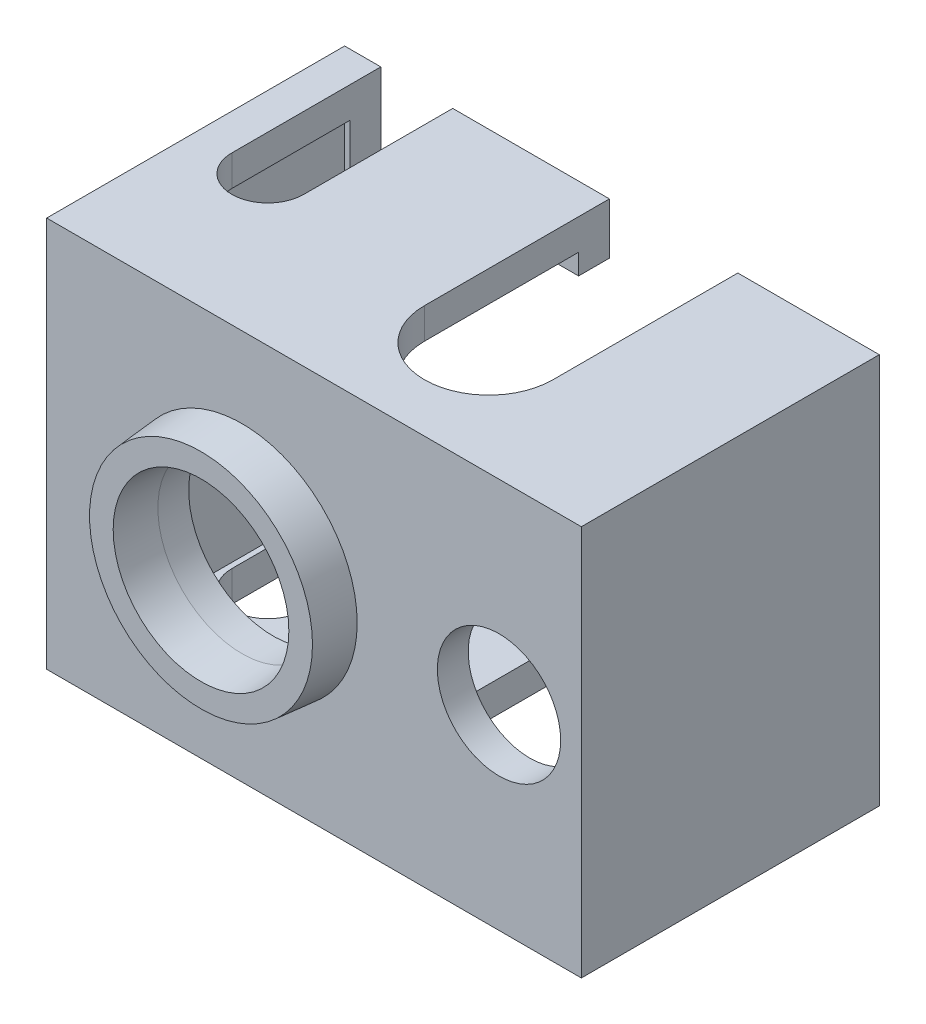
SolidWorks part; units mm, degrees
material "Silicon"
ref_plane "Front Plane" through (0, 0, 0) normal (0, 0, 1) x (1, 0, 0)
ref_plane "Top Plane" through (0, 0, 0) normal (0, 1, 0) x (1, 0, 0)
ref_plane "Right Plane" through (0, 0, 0) normal (1, 0, 0) x (0, 0, -1)
sketch "Sketch1" plane through (0, 0, 0) normal (0, 0, 1) x (1, 0, 0)
  line L0 (0, 0) -> (15.01, 0) construction
  line L1 (0, 0) -> (0, -8.01) construction
  line L2 (15, -7.5) -> (15, 7.5) construction
  line L3 (15.01, 8.01) -> (-8.01, 8.01)
  line L4 (15.01, 8.01) -> (15.01, -8.01)
  line L5 (15.01, -8.01) -> (-8.01, -8.01)
  line L6 (-8.01, 8.01) -> (-8.01, -8.01)
  line L7 (-8, -7.5) -> (-8, 7.5) construction
  line L8 (14.5, -8) -> (-7.5, -8) construction
  line L9 (-9.51, 9.51) -> (-9.51, -9.51)
  line L10 (16.51, -9.51) -> (-9.51, -9.51)
  line L11 (16.51, 9.51) -> (16.51, -9.51)
  line L12 (16.51, 9.51) -> (-9.51, 9.51)
  point P8 (15.01, 0)
  point P9 (0, -9.3747)
  point P20 (-11.0812, -11.0812)
  dimension "D1" = 0.01
  dimension "D2" = 0.01
  dimension "D3" = 0.01
  dimension "D4" = 1.5
extrude "Boss-Extrude1" add sketch "Sketch1" against normal blind 11.5
sketch "Sketch2" plane through (0, 0, -11.5) normal (0, 0, -1) x (-1, 0, 0)
  line L4 (9.51, 9.51) -> (-16.51, 9.51)
  line L5 (-16.51, 9.51) -> (-16.51, -9.51)
  line L6 (-16.51, -9.51) -> (9.51, -9.51)
  line L7 (9.51, -9.51) -> (9.51, 9.51)
  line L8 (9.51, 9.51) -> (-16.51, 9.51)
  line L9 (-16.51, 9.51) -> (-16.51, -9.51)
  line L10 (-16.51, -9.51) -> (9.51, -9.51)
  line L11 (9.51, -9.51) -> (9.51, 9.51)
  line L22 (7.01, -7.01) -> (7.01, 7.01)
  line L23 (-14.01, -7.01) -> (7.01, -7.01)
  line L24 (-14.01, 7.01) -> (-14.01, -7.01)
  line L25 (7.01, 7.01) -> (-14.01, 7.01)
  line L26 (7.01, -7.01) -> (7.01, 7.01)
  line L27 (-14.01, -7.01) -> (7.01, -7.01)
  line L28 (-14.01, 7.01) -> (-14.01, -7.01)
  line L29 (7.01, 7.01) -> (-14.01, 7.01)
  dimension "D1" = 0
  dimension "D2" = 1
extrude "Boss-Extrude2" add sketch "Sketch2" along normal blind 1.5
sketch "Sketch3" plane through (0, 0, 0) normal (0, 0, 1) x (1, 0, 0)
  line L4 (16.51, 9.51) -> (-9.51, 9.51)
  line L5 (-9.51, 9.51) -> (-9.51, -9.51)
  line L6 (-9.51, -9.51) -> (16.51, -9.51)
  line L7 (16.51, -9.51) -> (16.51, 9.51)
  line L8 (16.51, 9.51) -> (-9.51, 9.51)
  line L9 (-9.51, 9.51) -> (-9.51, -9.51)
  line L10 (-9.51, -9.51) -> (16.51, -9.51)
  line L11 (16.51, -9.51) -> (16.51, 9.51)
  circle A0 centre (0, 0) radius 4.1
  dimension "D2" = 8.2
  dimension "D1" = 0
extrude "Boss-Extrude3" add sketch "Sketch3" along normal blind 1.5
ref_axis "Axis1" through (0, 0, 1.5) along (0, 0, -1)
sketch "Sketch4" plane through (0, 0, 1.5) normal (0, 0, 1) x (1, 0, 0)
  circle A0 centre (0, 0) radius 4.1 construction
  circle A1 centre (0, 0) radius 4.1
  circle A2 centre (0, 0) radius 5.6
  dimension "D1" = 1.5
extrude "Boss-Extrude4" add sketch "Sketch4" along normal blind 2 draft 5
sketch "Sketch5" plane through (0, 0, 1.5) normal (0, 0, 1) x (1, 0, 0)
  circle A0 centre (12.5025, 0) radius 3
  dimension "D1" = 6
extrude "Cut-Extrude1" cut sketch "Sketch5" against normal up to surface (1.5 mm away) up to face at (3.5, 0, 0)
sketch "Sketch6" plane through (0, -9.51, 0) normal (0, -1, 0) x (1, 0, 0)
  line L0 (3.375, -4) -> (3.375, -13)
  line L1 (3.375, -13) -> (9.625, -13)
  line L2 (9.625, -13) -> (9.625, -4)
  line L3 (16.51, -13) -> (-9.51, -13) construction
  line L4 (-4.25, -5.75) -> (-4.25, -13)
  line L5 (-4.25, -13) -> (-7.75, -13)
  line L6 (-7.75, -13) -> (-7.75, -5.75)
  arc A0 (9.625, -4) -> (3.375, -4) centre (6.5, -4) ccw
  arc A1 (-4.25, -5.75) -> (-7.75, -5.75) centre (-6, -5.75) ccw
  dimension "D1" = 6.25
  dimension "D2" = 3.5
extrude "Cut-Extrude2" cut sketch "Sketch6" against normal through all
